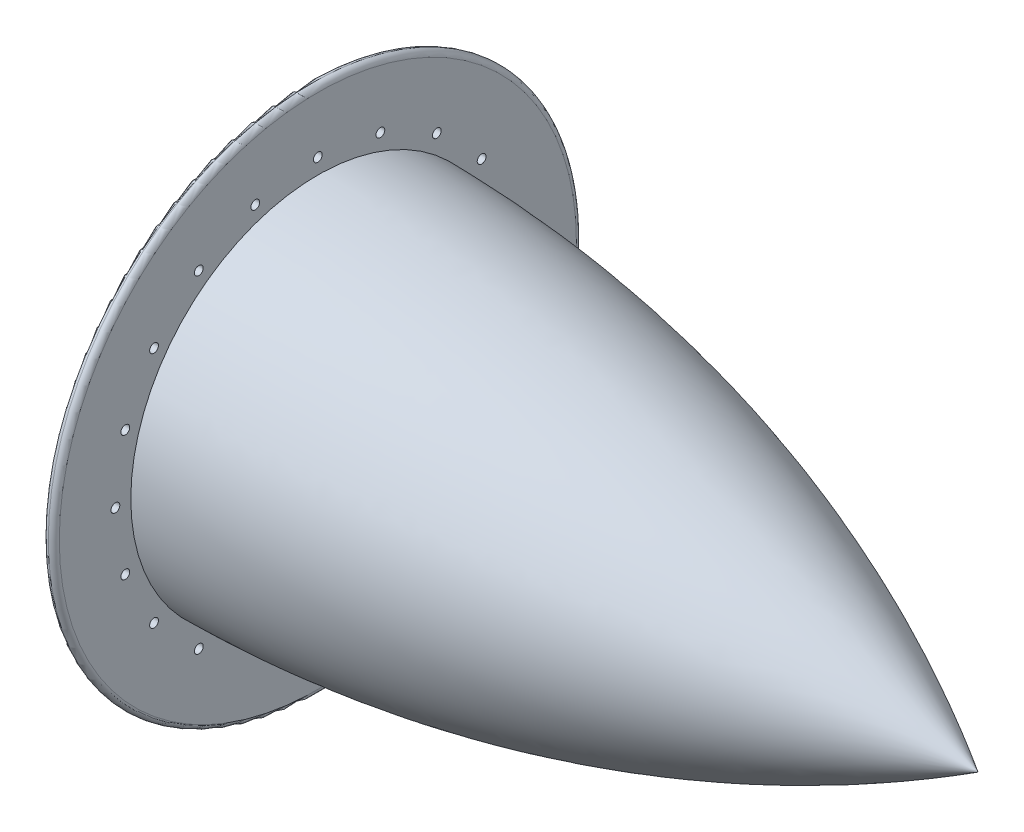
SolidWorks part; units mm, degrees
ref_plane "Front Plane" through (0, 0, 0) normal (0, 0, 1) x (1, 0, 0)
ref_plane "Top Plane" through (0, 0, 0) normal (0, 1, 0) x (1, 0, 0)
ref_plane "Right Plane" through (0, 0, 0) normal (1, 0, 0) x (0, 0, -1)
sketch "Sketch1" plane through (0, 0, 0) normal (0, 0, 1) x (1, 0, 0)
  line L0 (-151.6779, 0) -> (270.3701, 0) construction
  line L1 (-81.643, 0) -> (-81.643, 85)
  line L2 (-81.643, 0) -> (218.357, 0)
  arc A0 (-81.643, 85) -> (218.357, 0) centre (-87.9444, -509.1522) cw
  dimension "D1" = 85
  dimension "D2" = 300
revolve "Revolve1" add sketch "Sketch1" angle 360 about L0
shell "Shell1" thickness 5 removed face at (-81.643, 0, 85)
sketch "Sketch3" plane through (-81.643, 0, 0) normal (-1, 0, 0) x (0, 0, 1)
  circle A1 centre (0, 0) radius 120
  circle A2 centre (0, 0) radius 79.9997 construction
  circle A3 centre (0, 0) radius 79.9997
  dimension "D1" = 240
extrude "Boss-Extrude1" add sketch "Sketch3" along normal blind 5
sketch "Sketch4" plane through (-86.643, 0, 0) normal (-1, 0, 0) x (0, 0, 1)
  circle A0 centre (0, 92) radius 2
  circle A1 centre (28.4296, 87.4972) radius 2
  circle A2 centre (54.0762, 74.4296) radius 2
  circle A3 centre (74.4296, 54.0762) radius 2
  circle A4 centre (87.4972, 28.4296) radius 2
  circle A5 centre (92, 0) radius 2
  circle A6 centre (87.4972, -28.4296) radius 2
  circle A7 centre (74.4296, -54.0762) radius 2
  circle A8 centre (54.0762, -74.4296) radius 2
  circle A9 centre (28.4296, -87.4972) radius 2
  circle A10 centre (0, -92) radius 2
  circle A11 centre (-28.4296, -87.4972) radius 2
  circle A12 centre (-54.0762, -74.4296) radius 2
  circle A13 centre (-74.4296, -54.0762) radius 2
  circle A14 centre (-87.4972, -28.4296) radius 2
  circle A15 centre (-92, 0) radius 2
  circle A16 centre (-87.4972, 28.4296) radius 2
  circle A17 centre (-74.4296, 54.0762) radius 2
  circle A18 centre (-54.0762, 74.4296) radius 2
  circle A19 centre (-28.4296, 87.4972) radius 2
  point P43 (0, 0)
  dimension "D1" = 4
  dimension "D2" = 92
  dimension "D3" = 20
extrude "Cut-Extrude1" cut sketch "Sketch4" against normal blind 5
fillet "Fillet1" radius 2.5 2 edges at (-81.643, 0, 120) (-86.643, 0, 120)
